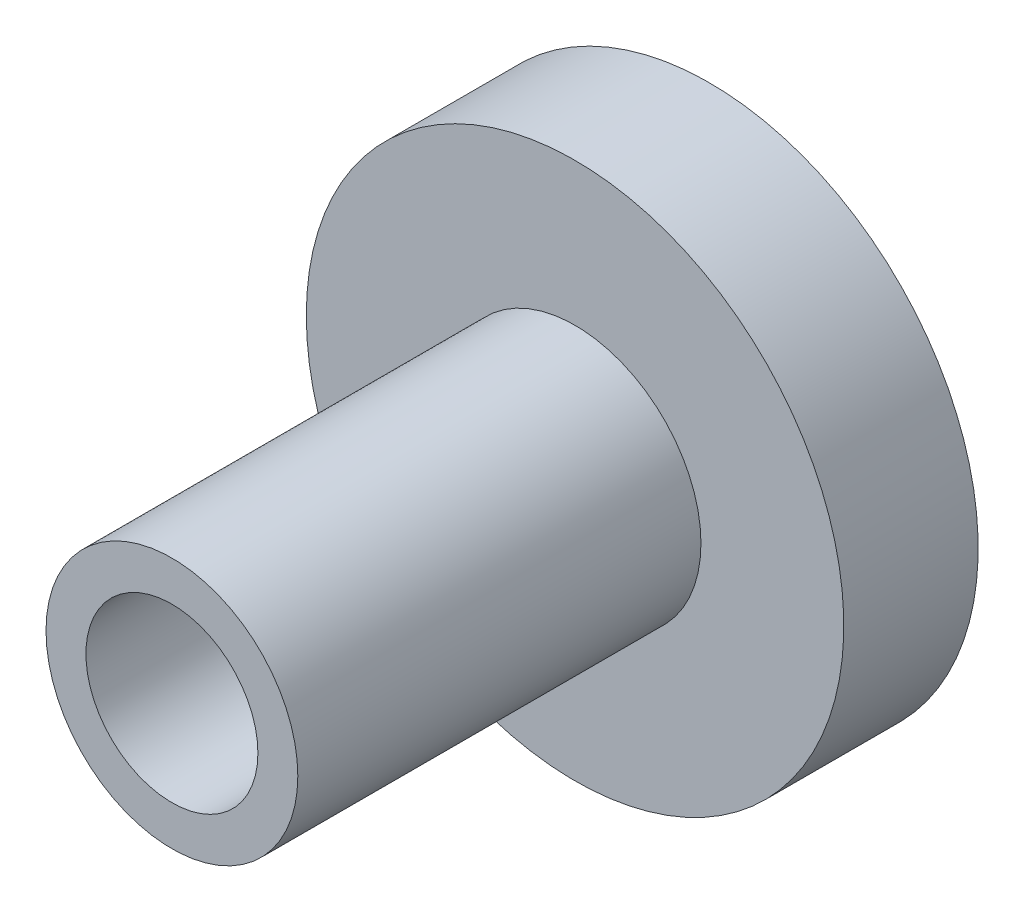
SolidWorks part; units mm, degrees
ref_plane "Front Plane" through (0, 0, 0) normal (0, 0, 1) x (1, 0, 0)
ref_plane "Top Plane" through (0, 0, 0) normal (0, 1, 0) x (1, 0, 0)
ref_plane "Right Plane" through (0, 0, 0) normal (1, 0, 0) x (0, 0, -1)
sketch "Sketch1" plane through (0, 0, 0) normal (0, 0, 1) x (1, 0, 0)
  circle A0 centre (0, 0) radius 5.95
  dimension "D1" = 11.9
extrude "Boss-Extrude1" add sketch "Sketch1" along normal blind 19.05
sketch "Sketch2" plane through (0, 0, 0) normal (0, 0, -1) x (-1, 0, 0)
  circle A0 centre (0, 0) radius 12.7
  dimension "D1" = 25.4
extrude "Boss-Extrude2" add sketch "Sketch2" along normal blind 6.35
sketch "Sketch3" plane through (0, 0, 19.05) normal (0, 0, 1) x (1, 0, 0)
  circle A0 centre (0, 0) radius 4.064
  dimension "D1" = 8.128
extrude "Cut-Extrude1" cut sketch "Sketch3" against normal offset from surface (15.875 mm away) 3.175 up to face at (5.95, 0, 0)
hole_wizard "CSK for #8 Flat Head Machine Screw (100)1" positions "Sketch4" profile "Sketch6" countersink size "#8" standard "ANSI Inch" end condition up to next
sketch "Sketch4" plane through (0, 0, 3.175) normal (0, 0, 1) x (1, 0, 0)
  point P0 (0, 0)
sketch "Sketch6" plane through (0, 0, 3.175) normal (1, 0, 0) x (0, -1, 0)
  line L0 (0, 0) -> (0, 9.525)
  line L1 (0, 9.525) -> (2.2479, 9.525)
  line L2 (2.2479, 9.525) -> (2.2479, 1.6518)
  line L3 (2.2479, 1.6518) -> (4.2164, 0)
  line L5 (4.2164, 0) -> (0, 0)
  line L6 (-2.2479, 1.6518) -> (-4.2164, 0) construction
  line L11 (0, -6.35) -> (0, 107.95) construction
  dimension "Thru Hole Dia." = 4.4958
  dimension "Thru Hole Depth" = 9.525
  dimension "Near C'Sink Dia." = 8.4328
  dimension "Near C'Sink Angle" = 100
sketch "Sketch7" plane through (0, 0, 3.175) normal (0, 0, -1) x (-1, 0, 0)
  circle A0 centre (0, 0) radius 4.064 construction
  circle A1 centre (0, 0) radius 4.2164
  circle A2 centre (0, 0) radius 4.2164
  circle A3 centre (0, 0) radius 4.064
  dimension "D1" = 0
extrude "Boss-Extrude3" add sketch "Sketch7" along normal up to surface up to face at (2.2479, 0, 1.5232)
sketch "Sketch8" plane through (0, 0, -6.35) normal (0, 0, -1) x (-1, 0, 0)
  line L1 (2.5297, -4.3815) -> (5.0593, 0)
  line L2 (5.0593, 0) -> (2.5297, 4.3815)
  line L3 (2.5297, 4.3815) -> (-2.5297, 4.3815)
  line L4 (-2.5297, 4.3815) -> (-5.0593, 0)
  line L5 (-5.0593, 0) -> (-2.5297, -4.3815)
  line L6 (-2.5297, -4.3815) -> (2.5297, -4.3815)
  circle A0 centre (0, 0) radius 4.3815 construction
  dimension "D1" = 8.763
extrude "Cut-Extrude2" cut sketch "Sketch8" against normal blind 4.7625
other "Move Face1" flip direction yes face at (3.7945, 2.1907, -3.9688) face at (0, 4.3815, -3.9688) face at (-3.7945, 2.1908, -3.9688) face at (-3.7945, -2.1907, -3.9688) face at (0, -4.3815, -3.9688) face at (3.7945, -2.1907, -3.9688) offset 0.254 parameters "D1"=0.254
sketch "Sketch10" plane through (0, 0, 19.05) normal (0, 0, 1) x (1, 0, 0)
  line L0 (-5.1383, -3) -> (-5.1383, 3)
  circle A0 centre (0, 0) radius 5.95 construction
  dimension "D1" = 6
ref_plane "Plane2" through (-5.1383, 0, 0) normal (1, 0, 0) x (0, 1, 0)
sketch "Sketch9" plane through (-5.1383, 0, 0) normal (-1, 0, 0) x (0, 0, 1)
  line L0 (0, -5.95) -> (0, 5.95) construction
  line L1 (12, 3) -> (6, 3)
  line L2 (12, 3) -> (12, -3)
  line L3 (12, -3) -> (6, -3)
  line L4 (6, 3) -> (6, -3)
  line L5 (12, 3) -> (6, -3) construction
  line L6 (12, -3) -> (6, 3) construction
  point P0 (9, 0)
  point P7 (0, 0)
  point P10 (0, 0)
  dimension "D1" = 6
  dimension "D2" = 6
  dimension "D3" = 6
extrude "Cut-Extrude3" cut sketch "Sketch9" along normal through all
draft "Draft1" type of draft neutral plane draft angle 65 faces to draft 2 face at (-5.5442, 0, 12) face at (-5.5442, 0, 6) neutral plane through (-5.1383, 0, 0) neutral plane normal (-1, 0, 0) parameters "D1"=65
